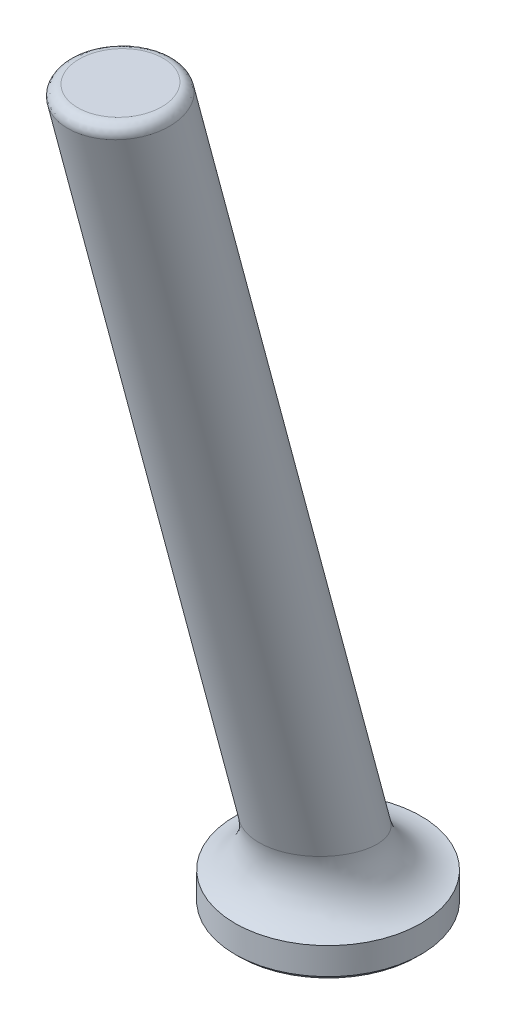
SolidWorks part; units mm, degrees
ref_plane "前视基准面" through (0, 0, 0) normal (0, 0, 1) x (1, 0, 0)
ref_plane "上视基准面" through (0, 0, 0) normal (0, 1, 0) x (1, 0, 0)
ref_plane "右视基准面" through (0, 0, 0) normal (1, 0, 0) x (0, 0, -1)
other "Configuration Table"
sketch "草图1" plane through (0, 0, 0) normal (0, 1, 0) x (1, 0, 0)
  circle A0 centre (0, 0) radius 9
  dimension "D1" = 18
extrude "凸台-拉伸1" add sketch "草图1" along normal blind 3
sketch "草图3" plane through (0, 3, 0) normal (0, 1, 0) x (1, 0, 0)
  line L0 (0, 0) -> (8.5213, 0) construction
ref_axis "基准轴1" through (0, 3, 0) along (1, 0, 0)
ref_plane "基准面1" through (0, 2.799, 0.75) normal (0, 0.9659, 0.2588) x (1, 0, 0)
sketch "草图4" plane through (0, 2.799, 0.75) normal (0, 0.9659, 0.2588) x (1, 0, 0)
  circle A0 centre (0, 0.7765) radius 5
  dimension "D1" = 10
extrude "凸台-拉伸2" add sketch "草图4" along normal blind 90 and the other way blind 10
sketch "草图5" plane through (0, 0, 0) normal (0, -1, 0) x (-1, 0, 0)
  circle A0 centre (0, 0) radius 9.8153
extrude "切除-拉伸1" cut sketch "草图5" along normal blind 20
fillet "圆角1" radius 5 1 edges at (0, 3, 5.1764)
ref_plane "基准面2" through (0, 80, 0) normal (0, -1, 0) x (-1, 0, 0)
sketch "草图6" plane through (0, 80, 0) normal (0, -1, 0) x (-1, 0, 0)
  circle A0 centre (-9.3455, -17.9129) radius 22.2417
extrude "切除-拉伸2" cut sketch "草图6" against normal blind 21 and the other way blind 1
chamfer "倒角2" distance 0.4 angle 45 1 edges at (0, 0, 9)
sketch "草图7" plane through (0, 0, 0) normal (0, -1, 0) x (-1, 0, 0)
  circle A0 centre (0, 0) radius 1.45
  dimension "D1" = 2.9
extrude "切除-拉伸3" cut sketch "草图7" against normal blind 12
fillet "圆角3" radius 1 1 edges at (0, 79, 25.5405)
